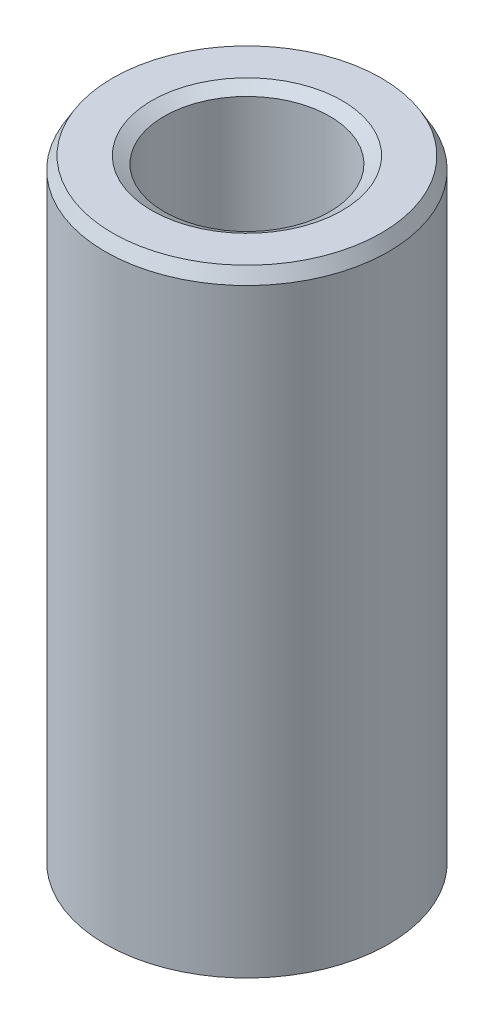
SolidWorks part; units mm, degrees
ref_plane "Front Plane" through (0, 0, 0) normal (0, 0, 1) x (1, 0, 0)
ref_plane "Top Plane" through (0, 0, 0) normal (0, 1, 0) x (1, 0, 0)
ref_plane "Right Plane" through (0, 0, 0) normal (1, 0, 0) x (0, 0, -1)
sketch "Sketch1" plane through (0, 0, 0) normal (0, 1, 0) x (1, 0, 0)
  circle A0 centre (0, 0) radius 10
  dimension "SLEEVE_OD" = 20
extrude "Boss-Extrude1" add sketch "Sketch1" along normal blind 43.7422
sketch "Sketch2" plane through (0, 0, 0) normal (0, 1, 0) x (1, 0, 0)
  circle A0 centre (0, 0) radius 5.8442
  dimension "BORE_D" = 11.6884
extrude "Cut-Extrude1" cut sketch "Sketch2" along normal through all
chamfer "Chamfer1" distance 0.8798 angle 30.357 4 edges at (0, 43.7422, 5.8442) (0, 0, 5.8442) (0, 0, 10) (0, 43.7422, 10) first distance on face at (0, 43.7422, 5.8442) first distance on face at (0, 0, 5.8442) first distance on face at (0, 43.7422, 10)
